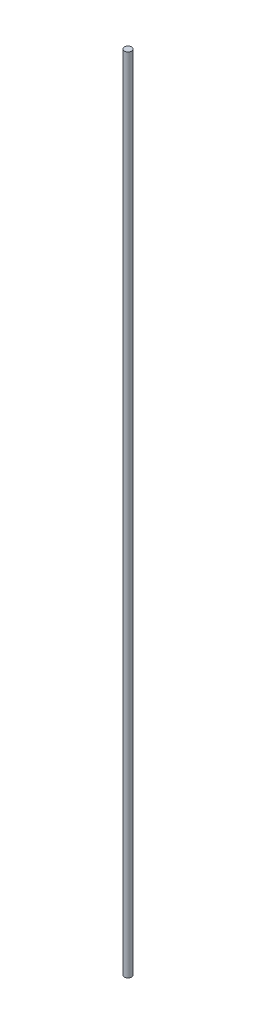
SolidWorks part; units mm, degrees
ref_plane "Спереди" through (0, 0, 0) normal (0, 0, 1) x (1, 0, 0)
ref_plane "Сверху" through (0, 0, 0) normal (0, 1, 0) x (1, 0, 0)
ref_plane "Справа" through (0, 0, 0) normal (1, 0, 0) x (0, 0, -1)
sketch "Эскиз2" plane through (0, 0, 0) normal (0, 0, 1) x (1, 0, 0)
  line L5 (-2.5, 275) -> (0, 275)
  line L6 (-2.5, 275) -> (-2.5, -275)
  line L7 (-2.5, -275) -> (0, -275)
  line L8 (0, 275) -> (0, -275)
  line L9 (-2.5, 275) -> (0, -275) construction
  line L10 (-2.5, -275) -> (0, 275) construction
  point P0 (-1.25, 0)
  point P5 (0, 0)
  dimension "D1" = 2.5
  dimension "D2" = 550
revolve "Повернуть1" add sketch "Эскиз2" angle 360 about L6
equation "\"Ширина груза\"= 420"
equation "\"Глубина груза\"= 490"
equation "\"Высота груза\"= 297"
equation "\"Ширина ячейки\"= \"Ширина груза\" + 10"
equation "\"Глубина ячейки\"= \"Глубина груза\" + 10"
equation "\"Высота ячейки\"= \"Высота груза\" + 10 + 13"
equation "\"Колво ячеек ширина\"= 2"
equation "\"Колво ячеек высота\"= 2"
equation "\"Толщина стенки\"= 10"
equation "\"Крепление дверцы\"= 5"
equation "\"Ширина рейки\"= \"Толщина шестерни\""
equation "\"Высота рейки\"= 20"
equation "\"Высота пола\"= 20"
equation "\"Колво полозьев\"= 5"
equation "\"Отступ рейки\"= 20"
equation "\"Глубина каретки\"= \"Глубина ячейки\" + 30 + \"Мотор Y высота корпуса\" + 20"
equation "\"Длинна рейки\"= ( \"Ширина ячейки\" + \"Толщина стенки\" + \"Крепление дверцы\" ) * \"Колво ячеек ширина\" + \"Ширина ячейки выгрузки\" * \"Колво выгрузки\" + \"Толщина стенки\""
equation "\"Отступ шпильки\"= 26"
equation "\"Диаметр шпильки\"= 5"
equation "\"Длинна шпильки\"= ( \"Высота ячейки\" + \"Толщина стенки\" + \"Высота пола\" ) * \"Колво ячеек высота\" + ( \"Толщина стенки\" + \"Отступ рейки\" ) * 2 "
equation "\"D1@Эскиз2\"= \"Диаметр шпильки\" / 2"
equation "\"D2@Эскиз2\"= \"Глубина каретки\" - \"Мотор Y высота корпуса\""
equation "\"Ширина пластины\"= 50  "
equation "\"Высота зона выгрузки\"= \"Высота ячейки\" * 2 + \"Толщина стенки\" * 2"
equation "\"Колво выгрузки\"= 1"
equation "\"Отступ крепления мотора фиксации\" = 30"
equation "\"Мотор X ширина корпуса\"= 42.3"
equation "\"Мотор X высота корпуса\"= 42.3"
equation "\"Мотор X длина корпуса\"= 40"
equation "\"Мотор X вылет вала\"= 19.8"
equation "\"Мотор Y ширина корпуса\"= 42.3"
equation "\"Мотор Y высота корпуса\"= 42.3"
equation "\"Мотор Y длина корпуса\"= 48"
equation "\"Мотор Y вылет вала\"= 30"
equation "\"Мотор Z ширина корпуса\"= 42"
equation "\"Мотор Z высота корпуса\"= 42"
equation "\"Мотор Z длина корпуса\"= 40"
equation "\"Мотор Z вылет вала\"= 23"
equation "\"Мотор диаметр вала ПРЕДВ\"= 5"
equation "\"Мотор шаг крепления ПРЕДВ\"= 31"
equation "\"Мотор диаметр отверстий ПРЕДВ\"= 3"
equation "\"Мотор глубина отверстий ПРЕДВ\"= 4.5"
equation "\"Мотор диаметр буртика ПРЕДВ\"= 22"
equation "\"Мотор высота буртика ПРЕДВ\"= 2"
equation "\"Мотор диаметр шкива ПРЕДВ\"= 16"
equation "\"Мотор длина шкива ПРЕДВ\"= 12"
equation "\"Мотор отступ шкива ПРЕДВ\"= 5"
equation "\"Мотор X шаг градусов\"= 1.8"
equation "\"Мотор X ток А\"= 1.5"
equation "\"Мотор X сопротивление Ом\"= 1.3"
equation "\"Мотор X индуктивность мГн\"= 2"
equation "\"Мотор Y шаг градусов\"= 1.8"
equation "\"Мотор Y ток А\"= 2.2"
equation "\"Мотор Y сопротивление Ом\"= 0.9"
equation "\"Мотор Y индуктивность мГн\"= 2"
equation "\"Мотор Z шаг градусов\"= 1.8"
equation "\"Мотор Z ток А\"= 1"
equation "\"Мотор Z сопротивление Ом\"= 4"
equation "\"Мотор Z индуктивность мГн\"= 8"
equation "\"Мотор Y диаметр ротора\"= 25.78"
equation "\"Ширина ячейки выгрузки\"= \"Ширина ячейки\" + \"Толщина стенки\" + \"Отступ крепления мотора фиксации\"*2"
